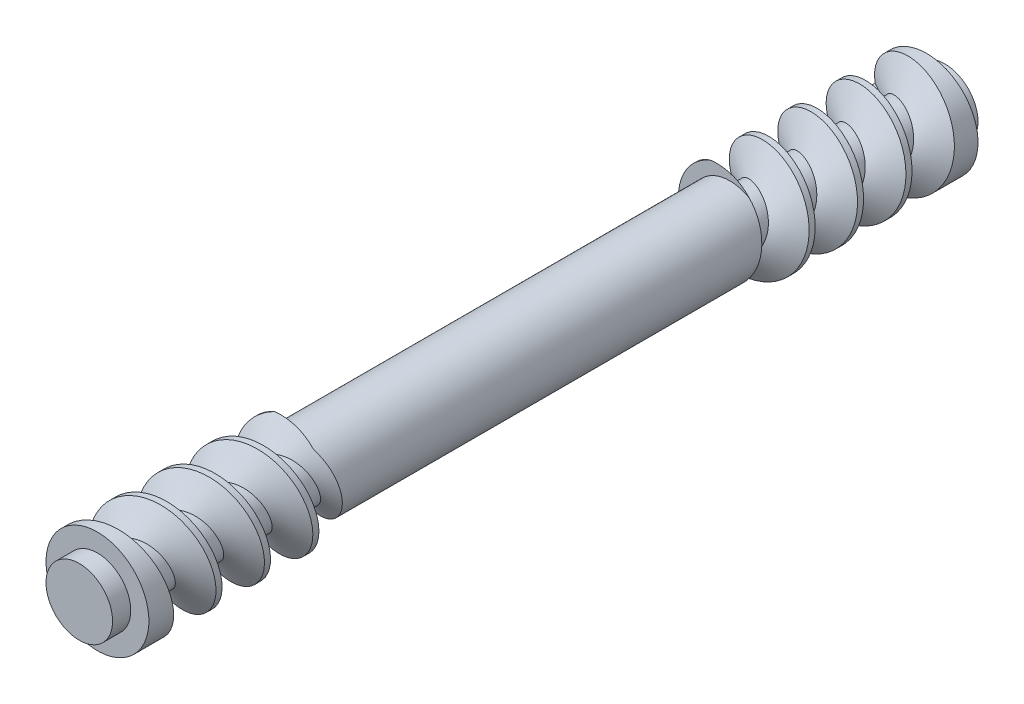
SolidWorks part; units mm, degrees
material "Acier non allié"
ref_plane "Plan de face" through (0, 0, 0) normal (0, 0, 1) x (1, 0, 0)
ref_plane "Plan de dessus" through (0, 0, 0) normal (0, 1, 0) x (1, 0, 0)
ref_plane "Plan de droite" through (0, 0, 0) normal (1, 0, 0) x (0, 0, -1)
sketch "Esquisse1" plane through (0, 0, 0) normal (0, 0, 1) x (1, 0, 0)
  circle A0 centre (0, 0) radius 4.25
  dimension "D1" = 8.5
extrude "Boss.-Extru.1" add sketch "Esquisse1" along normal mid plane 68.5
sketch "Esquisse3" plane through (0, 0, 34.25) normal (0, 0, 1) x (1, 0, 0)
  circle A0 centre (0, 0) radius 2.75
  dimension "D1" = 5.5
extrude "Boss.-Extru.2" add sketch "Esquisse3" along normal blind 1.5
mirror "Symétrie1" about plane through (0, 0, 0) normal (0, 0, 1) of "Boss.-Extru.2"
thread "Filetage1" pitch 4 method cut profile "Profil de filetage1" start angle 0, offset 0, length 15, pitch 4, diameter 8.5
ref_plane "Plan1" through (-4.25, 0, 34.25) normal (0, -1, 0) x (-1, 0, 0)
sketch "Profil de filetage1" plane through (-4.25, 0, 34.25) normal (0, -1, 0) x (-1, 0, 0)
  line L0 (0, 0) -> (0, 4) construction
  line L11 (0, 0) -> (0, 3.5)
  line L12 (0, 3.5) -> (-2.1651, 2.25)
  line L13 (-2.1651, 2.25) -> (-2.1651, 1.25)
  line L15 (-2.1651, 1.25) -> (0, 0)
  line L17 (-2.1651, 1.75) -> (0, 1.75) construction
  point P2 (0, 0)
  dimension "Pitch" = 4
  dimension "Profile_Angle" = 60
  dimension "Profile_Land" = 1
  dimension "Profile_Height" = 2.1651
mirror "Symétrie4" about plane through (0, 0, 0) normal (0, 0, 1) of "Filetage1"
sketch "Esquisse4" plane through (0, 0, 0) normal (0, 0, 1) x (1, 0, 0)
  circle A0 centre (0, 0) radius 3.25
  circle A2 centre (0, 0) radius 4.25 construction
  circle A3 centre (0, 0) radius 4.25
  dimension "D1" = 1
  dimension "D2" = 1
extrude "Enlèv. mat.-Extru.2" cut sketch "Esquisse4" along normal blind 18
mirror "Symétrie5" about plane through (0, 0, 0) normal (0, 0, 1) of "Enlèv. mat.-Extru.2"
